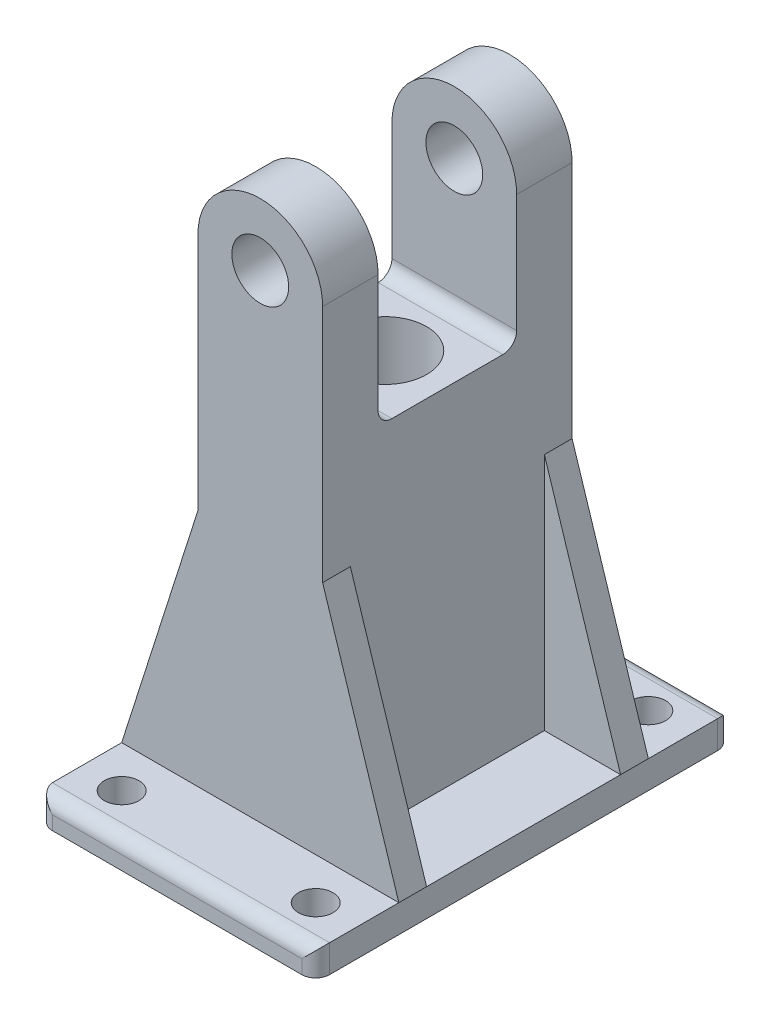
SolidWorks part; units mm, degrees
ref_plane "Спереди" through (0, 0, 0) normal (0, 0, 1) x (1, 0, 0)
ref_plane "Сверху" through (0, 0, 0) normal (0, 1, 0) x (1, 0, 0)
ref_plane "Справа" through (0, 0, 0) normal (1, 0, 0) x (0, 0, -1)
sketch "Эскиз1" plane through (0, 0, 0) normal (0, 0, 1) x (1, 0, 0)
  line L0 (-9, 0) -> (-9, -73)
  line L1 (-9, -73) -> (9, -73)
  line L2 (9, -73) -> (9, 0)
  circle A0 centre (0, 0) radius 4.1
  arc A1 (9, 0) -> (-9, 0) centre (0, 0) ccw
  dimension "D1" = 8.2
  dimension "D2" = 18
  dimension "D3" = 73
extrude "Бобышка-Вытянуть1" add sketch "Эскиз1" along normal blind 18 and the other way blind 18
sketch "Эскиз3" plane through (0, -73, 0) normal (0, -1, 0) x (1, 0, 0)
  line L1 (20, -30) -> (-20, -30)
  line L2 (20, -30) -> (20, 30)
  line L3 (20, 30) -> (-20, 30)
  line L4 (-20, -30) -> (-20, 30)
  line L5 (20, -30) -> (-20, 30) construction
  line L6 (20, 30) -> (-20, -30) construction
  point P0 (0, 0)
  dimension "D1" = 40
  dimension "D2" = 60
extrude "Бобышка-Вытянуть2" add sketch "Эскиз3" against normal blind 4
sketch "Эскиз4" plane through (0, -69, 0) normal (0, 1, 0) x (1, 0, 0)
  line L0 (9, -18) -> (9, 18) construction
  line L1 (-9, -10) -> (9, -10)
  line L2 (-9, -10) -> (-9, 10)
  line L3 (-9, 10) -> (9, 10)
  line L4 (9, -10) -> (9, 10)
  line L5 (-9, -10) -> (9, 10) construction
  line L6 (-9, 10) -> (9, -10) construction
  point P0 (0, 0)
  dimension "D1" = 20
extrude "Вырез-Вытянуть1" cut sketch "Эскиз4" along normal through all from offset 50
sketch "Эскиз5" plane through (0, -19, 0) normal (0, 1, 0) x (1, 0, 0)
  circle A0 centre (0, 0) radius 6
  dimension "D1" = 12
extrude "Вырез-Вытянуть2" cut sketch "Эскиз5" against normal through all
sketch "Эскиз6" plane through (0, 0, 0) normal (0, 0, 1) x (1, 0, 0)
  line L0 (-20, -69) -> (-9, -34.5)
  line L1 (-9, 0) -> (-9, -69) construction
  line L2 (-9, -34.5) -> (-9, -69)
  line L3 (-9, -69) -> (-20, -69)
  line L4 (9, -34.5) -> (20, -69)
  line L5 (9, -69) -> (9, 0) construction
  line L6 (20, -69) -> (9, -69)
  line L7 (9, -69) -> (9, -34.5)
extrude "Бобышка-Вытянуть3" add sketch "Эскиз6" against normal blind 4 from surface starting at face at (4.1, 0, 18)
extrude "Бобышка-Вытянуть4" add sketch "Эскиз6<3>" along normal blind 4 from surface starting at face at (4.1, 0, -18)
sketch "Эскиз6<3>" plane through (0, 0, 0) normal (0, 0, 1) x (1, 0, 0) same geometry as "Эскиз6"
sketch "Эскиз7" plane through (0, -69, 0) normal (0, 1, 0) x (1, 0, 0)
  line L0 (-20, -24) -> (-14, -24) construction
  line L1 (-20, -30) -> (-20, -18) construction
  line L2 (-14, -24) -> (-14, -30) construction
  line L3 (20, -30) -> (-20, -30) construction
  line L4 (0, 0) -> (-23.1784, 0) construction
  line L5 (0, 0) -> (0, 32.5836) construction
  circle A0 centre (-14, -24) radius 2.5
  circle A1 centre (-14, 24) radius 2.5
  circle A2 centre (14, 24) radius 2.5
  circle A3 centre (14, -24) radius 2.5
  dimension "D1" = 6
extrude "Вырез-Вытянуть4" cut sketch "Эскиз7" against normal through all
fillet "Скругление1" radius 2 8 edges at (0, -19, -10) (0, -19, 10) (-20, -71, -30) (0, -69, -30) (20, -71, -30) (0, -69, 30) (20, -71, 30) (-20, -71, 30)
